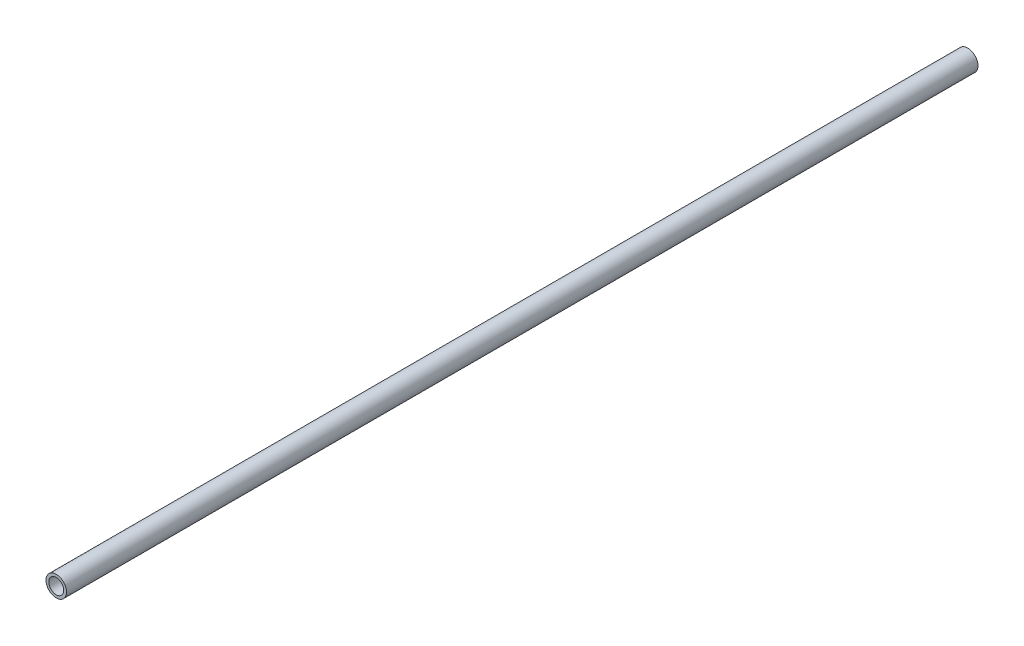
SolidWorks part; units mm, degrees
ref_plane "Front Plane" through (0, 0, 0) normal (0, 0, 1) x (1, 0, 0)
ref_plane "Top Plane" through (0, 0, 0) normal (0, 1, 0) x (1, 0, 0)
ref_plane "Right Plane" through (0, 0, 0) normal (1, 0, 0) x (0, 0, -1)
sketch "Sketch1" plane through (0, 0, 0) normal (0, 0, 1) x (1, 0, 0)
  circle A0 centre (0, 0) radius 8.5725
  dimension "Pipe OD" = 17.145
extrude "Extrude-Thin1" add sketch "Sketch1" along normal mid plane 762 thin thin type one direction reverse wall 2.3114
